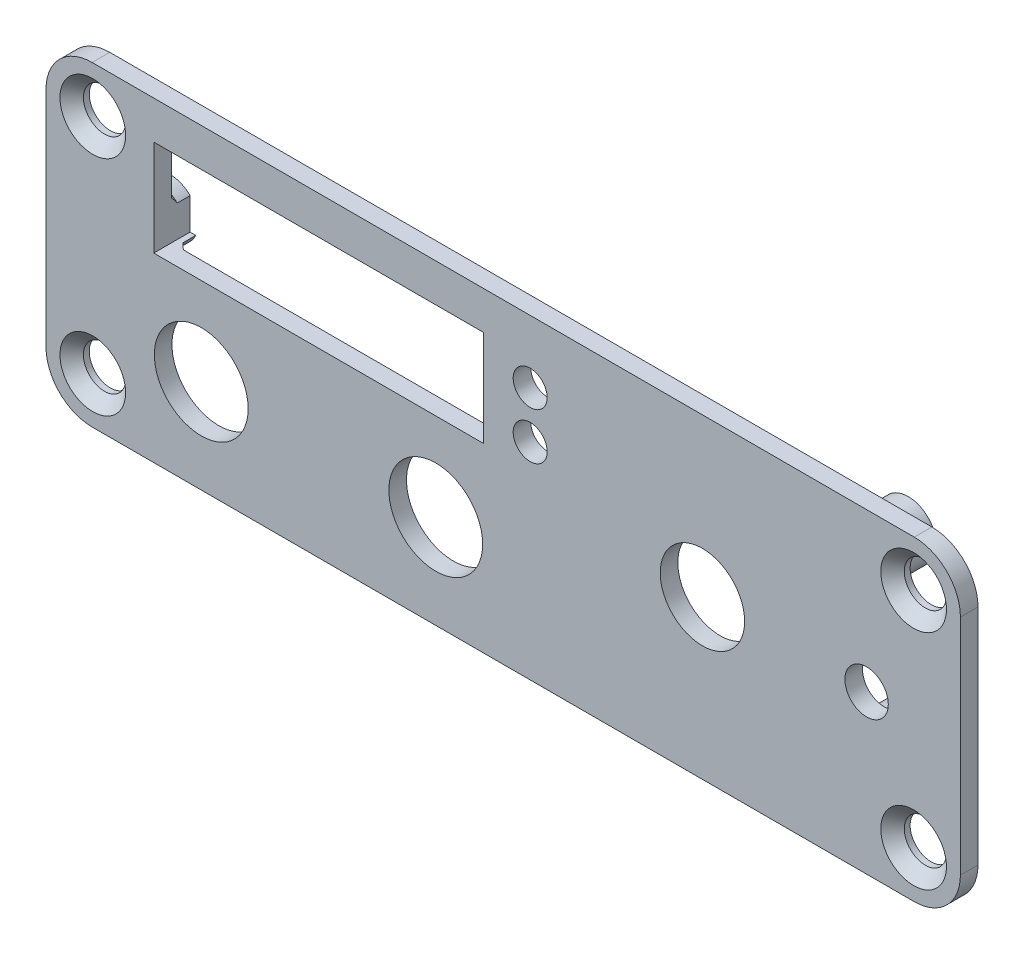
SolidWorks part; units mm, degrees
material "A-Glass Fiber"
ref_plane "Ebene vorne" through (0, 0, 0) normal (0, 0, 1) x (1, 0, 0)
ref_plane "Ebene oben" through (0, 0, 0) normal (0, 1, 0) x (1, 0, 0)
ref_plane "Ebene rechts" through (0, 0, 0) normal (1, 0, 0) x (0, 0, -1)
sketch "Sketch2" plane through (0, 0, 0) normal (0, 0, 1) x (1, 0, 0)
  line L0 (38.989, 0) -> (38.989, 26.924) construction
  line L1 (0, 13.462) -> (77.978, 13.462) construction
  line L2 (13.239, 8) -> (33.239, 8) construction
  line L3 (9.189, 19.574) -> (37.289, 19.574) construction
  line L4 (0, 22.989) -> (0, 3.935)
  line L5 (74.043, 26.924) -> (3.935, 26.924)
  line L6 (77.978, 3.935) -> (77.978, 22.989)
  line L7 (3.935, 0) -> (74.043, 0)
  line L8 (9.189, 23.674) -> (37.289, 23.674)
  line L9 (9.189, 23.674) -> (9.189, 15.474)
  line L10 (9.189, 15.474) -> (37.289, 15.474)
  line L11 (37.289, 23.674) -> (37.289, 15.474)
  line L12 (7.489, 22.962) -> (9.189, 22.962) construction
  line L13 (37.289, 22.412) -> (38.989, 22.412) construction
  circle A0 centre (3.989, 22.962) radius 1.8
  circle A1 centre (73.989, 22.962) radius 1.8
  circle A2 centre (3.989, 3.962) radius 1.8
  circle A3 centre (73.989, 3.962) radius 1.8
  arc A4 (0, 3.935) -> (3.935, 0) centre (3.935, 3.935) ccw
  arc A5 (3.935, 26.924) -> (0, 22.989) centre (3.935, 22.989) ccw
  arc A6 (77.978, 22.989) -> (74.043, 26.924) centre (74.043, 22.989) ccw
  arc A7 (74.043, 0) -> (77.978, 3.935) centre (74.043, 3.935) ccw
  circle A8 centre (3.989, 3.962) radius 3.5 construction
  circle A9 centre (55.978, 13.462) radius 3.6
  circle A10 centre (13.239, 8) radius 4
  circle A11 centre (33.239, 8) radius 4
  circle A12 centre (41.289, 21.574) radius 1.45
  circle A13 centre (41.289, 17.574) radius 1.45
  circle A14 centre (69.978, 13.462) radius 1.85
  circle A15 centre (55.978, 13.462) radius 8 construction
  circle A16 centre (13.239, 8) radius 5.65 construction
  circle A17 centre (3.989, 22.962) radius 3.5 construction
  point P29 (23.239, 15.474)
  point P35 (23.239, 8)
  dimension "D1" = 3.6
  dimension "D4" = 7.2
  dimension "D8" = 8
  dimension "D9" = 8
  dimension "D13" = 2.9
  dimension "D16" = 3.7
  dimension "D17" = 16
  dimension "D19" = 7
  dimension "D20" = 11.3
  dimension "D23" = 3.935
  dimension "D2" = 70
  dimension "D3" = 19
  dimension "D5" = 22
  dimension "D6" = 8
  dimension "D7" = 20
  dimension "D10" = 8.2
  dimension "D11" = 28.1
  dimension "D12" = 3.25
  dimension "D14" = 4
  dimension "D15" = 4
  dimension "D18" = 8
  dimension "D21" = 26.924
  dimension "D22" = 77.978
extrude "Boss-Extrude2" add sketch "Sketch2" along normal blind 1.5 separate body
sketch "Sketch3" plane through (0, 0, 0) normal (0, 0, -1) x (-1, 0, 0)
  line L0 (-8.389, 16.474) -> (-9.189, 16.474) construction
  line L1 (-9.189, 23.674) -> (-9.189, 15.474) construction
  line L3 (-41.289, 21.574) -> (-41.289, 17.574) construction
  line L4 (-9.189, 15.474) -> (-9.6707, 15.474)
  line L5 (-9.189, 15.474) -> (-37.289, 15.474) construction
  line L6 (-9.189, 15.474) -> (-9.189, 18.1681)
  circle A0 centre (-7.489, 16.474) radius 0.9
  arc A1 (-9.6707, 15.474) -> (-9.189, 18.1681) centre (-7.489, 16.474) ccw
  circle A2 centre (-46.239, 22.674) radius 0.9
  circle A3 centre (-46.239, 22.674) radius 2.4
  point P15 (-41.289, 19.574)
  point P16 (-9.189, 19.574)
  dimension "D1" = 1.8
  dimension "D2" = 4.8
  dimension "D4" = 4.95
  dimension "D3" = 1.7
  dimension "D5" = 3.1
  dimension "D6" = 3.1
extrude "Boss-Extrude3" add sketch "Sketch3" along normal blind 1.6
sketch "Sketch4" plane through (0, 0, 0) normal (0, 0, -1) x (-1, 0, 0)
  circle A0 centre (-67.228, 20.962) radius 0.9
  circle A2 centre (-67.228, 20.962) radius 2.4
  circle A4 centre (-69.978, 13.462) radius 1.85 construction
  circle A5 centre (-67.228, 5.962) radius 0.9
  circle A6 centre (-67.228, 5.962) radius 2.4
  circle A7 centre (-45.728, 5.962) radius 0.9
  circle A8 centre (-45.728, 5.962) radius 2.4
  dimension "D1" = 4.8
  dimension "D2" = 1.8
  dimension "D3" = 2.75
  dimension "D4" = 7.5
  dimension "D5" = 15
  dimension "D6" = 21.5
extrude "Boss-Extrude4" add sketch "Sketch4" along normal blind 4.8
chamfer "Chamfer1" distance 0.5 angle 45 5 edges at (5.1265, 16.0515, 0) (48.639, 22.674, 0) (48.128, 5.962, 0) (69.628, 20.962, 0) (69.628, 5.962, 0)
chamfer "Chamfer2" distance 1 angle 45 4 edges at (75.789, 3.962, 1.5) (75.789, 22.962, 1.5) (5.789, 22.962, 1.5) (5.789, 3.962, 1.5)
